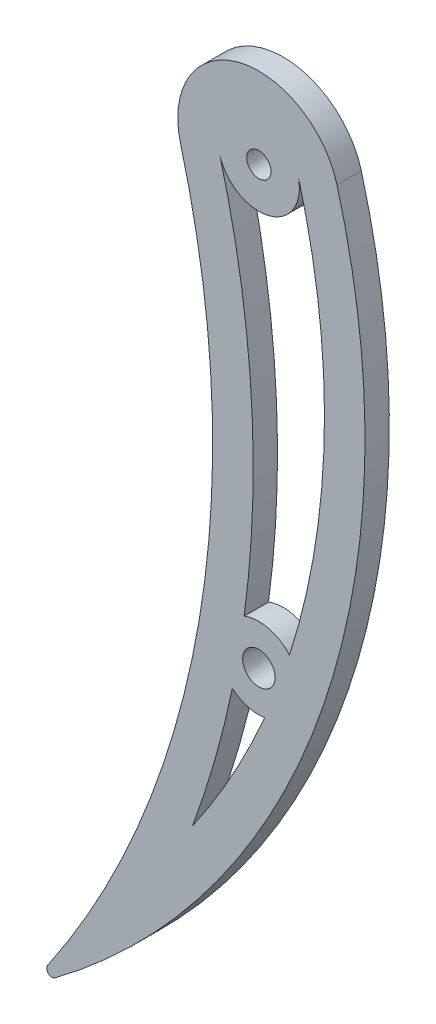
SolidWorks part; units mm, degrees
material "Plain Carbon Steel"
ref_plane "Front Plane" through (0, 0, 0) normal (0, 0, 1) x (1, 0, 0)
ref_plane "Top Plane" through (0, 0, 0) normal (0, 1, 0) x (1, 0, 0)
ref_plane "Right Plane" through (0, 0, 0) normal (1, 0, 0) x (0, 0, -1)
sketch "Sketch1" plane through (0, 0, 0) normal (0, 0, 1) x (1, 0, 0)
  line L0 (5.1445, 48.6362) -> (5.1445, -5.1638)
  line L1 (-21.7555, -51.7438) -> (5.1445, -5.1638)
  line L2 (-17.4256, -54.2443) -> (10.1445, -6.5038)
  line L3 (0.1445, 48.6362) -> (0.1445, -5.1638)
  line L4 (10.1445, 48.6362) -> (10.1445, -5.1638)
  line L5 (10.1445, 48.6362) -> (10.1445, -6.5038)
  line L6 (-26.0853, -49.2433) -> (0.1445, -3.8237)
  line L7 (0.1445, 48.6362) -> (0.1445, -3.8237)
  circle A0 centre (5.1445, 48.6362) radius 1.5
  circle A1 centre (-21.7555, -51.7438) radius 2
  arc A2 (-17.4256, -54.2443) -> (-26.0853, -49.2433) centre (-21.7555, -51.7438) cw
  arc A3 (0.1445, 48.6362) -> (10.1445, 48.6362) centre (5.1445, 48.6362) cw
  circle A4 centre (5.1445, -5.1638) radius 2
  arc A5 (10.1445, 48.6362) -> (0.1445, 48.6362) centre (5.1445, 48.6362) ccw
  circle A6 centre (-95.2141, 21.7362) radius 99.0802
  arc A7 (0.1445, -5.1638) -> (10.1445, -5.1638) centre (5.1445, -5.1638) ccw
  circle A8 centre (5.9967, -2.4738) radius 104.0661
  circle A9 centre (-95.2141, 21.7362) radius 108.8802
  dimension "D2" = 4
  dimension "D3" = 3
  dimension "D1" = 4
extrude "Extrude1" add sketch "Sketch1" along normal blind 3 contours A7 L3 L6 A2 L2 A1 | A2 A9 L2 | L5 A9 A3 L4 | A3 A9 A6 A7 A4 A0 L4 | L2 A9 A7 | A7 A9 L5 region at (6.16, 22.0557, 0) region at (-9.5246, -32.956, 0) region at (-2.7557, -31.6611, 0) region at (9.716, -7.2082, 0) region at (10.1257, -5.6796, 0) region at (11.555, 21.7384, 0)
sketch "Sketch3" plane through (0, 0, 0) normal (0, 0, -1) x (-1, 0, 0)
  circle A0 centre (-5.1445, -5.1638) radius 7.5 construction
  arc A1 (4.5159, 46.0523) -> (-14.7839, 51.2976) centre (-5.1445, 48.6362) ccw
  arc A2 (19.9834, -50.8165) -> (-14.7839, 51.2976) centre (77.6238, 25.7843) cw
  circle A3 centre (21.7555, -51.7438) radius 2 construction
  arc A4 (20.9096, -49.9314) -> (4.5159, 46.0523) centre (117.2126, 15.9087) cw
  arc A5 (19.9834, -50.8165) -> (20.9096, -49.9314) centre (20.3737, -50.2978) ccw
  arc M1 (-9.8312, 50.3783) -> (18.5686, -55.5965) centre (95.2141, 21.7362) ccw
  arc M2 (18.5686, -55.5965) -> (26.0853, -49.2433) centre (21.7555, -51.7438) ccw
  arc M3 (26.0853, -49.2433) -> (-0.1445, 48.6362) centre (95.2141, 21.7362) cw
  arc M4 (-0.1445, 48.6362) -> (-9.8312, 50.3783) centre (-5.1445, 48.6362) ccw
  circle M5 centre (21.7555, -51.7438) radius 2
  dimension "D1" = 15
  dimension "D2" = 20
extrude "Cut-Extrude1" cut sketch "Sketch3" against normal blind 10 contours A4 A2 M5 M1 M2 M3 region at (-15.9387, -38.3925, 0)
extrude "Boss-Extrude1" add sketch "Sketch3<3>" against normal blind 3 contours A4 A1 A2 M3 M1 M4 | A5 M5 region at (0.2001, 9.8384, 0) region at (-20.5766, -50.5101, 0)
sketch "Sketch3<3>" plane through (0, 0, 0) normal (0, 0, -1) x (-1, 0, 0) same geometry as "Sketch3"
sketch "Sketch4" plane through (0, 0, 0) normal (0, 0, -1) x (-1, 0, 0)
  arc A5 (-5.8494, -10.1138) -> (-1.879, -8.9501) centre (-5.1445, -5.1638) ccw
  arc A6 (-9.9642, 49.9669) -> (-0.363, 50.0981) centre (-5.1445, 48.6362) ccw
  arc A7 (-3.3338, -0.5032) -> (-8.9242, -1.8905) centre (-5.1445, -5.1638) ccw
  arc A8 (-1.879, -8.9501) -> (3.0469, -26.1266) centre (117.2126, 15.9087) ccw
  arc A9 (-5.8494, -10.1138) -> (3.0469, -26.1266) centre (77.6238, 25.7843) ccw
  arc A10 (-0.3143, 47.3443) -> (3.0469, -26.1266) centre (117.2126, 15.9087) ccw
  arc A11 (-0.3143, 47.3443) -> (-9.9642, 49.9669) centre (-5.1445, 48.6362) ccw
  arc A12 (-9.9642, 49.9669) -> (3.0469, -26.1266) centre (77.6238, 25.7843) ccw
  arc A13 (-0.3143, 47.3443) -> (-3.3338, -0.5032) centre (117.2126, 15.9087) ccw
  arc A14 (-0.3143, 47.3443) -> (-0.363, 50.0981) centre (-5.1445, 48.6362) ccw
  arc A15 (-9.9642, 49.9669) -> (-8.9242, -1.8905) centre (77.6238, 25.7843) ccw
  dimension "D2" = 5
  dimension "D1" = 5
extrude "Cut-Extrude2" cut sketch "Sketch4" against normal blind 5 contours A6 A15 A7 A13 | A5 A9 A8 region at (1.6968, -15.4545, 0) region at (7.9618, 23.9826, 0)
move or copy body "Body-Move/Copy1" [suppressed] bodies to move or copy 106
move or copy body "Body-Move/Copy2" [suppressed] bodies to move or copy 106
move or copy body "Body-Move/Copy3" [suppressed] bodies to move or copy 106
